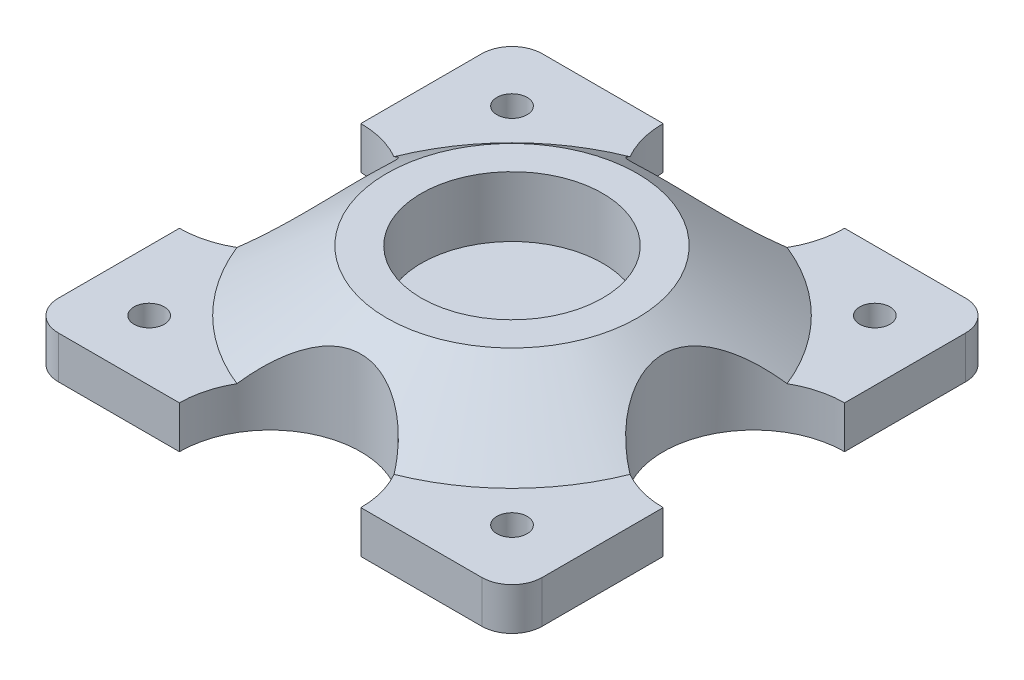
SolidWorks part; units mm, degrees
ref_plane "Front Plane" through (0, 0, 0) normal (0, 0, 1) x (1, 0, 0)
ref_plane "Top Plane" through (0, 0, 0) normal (0, 1, 0) x (1, 0, 0)
ref_plane "Right Plane" through (0, 0, 0) normal (1, 0, 0) x (0, 0, -1)
sketch "Sketch1" plane through (0, 0, 0) normal (0, 1, 0) x (1, 0, 0)
  line L1 (50.8, -50.8) -> (-50.8, -50.8)
  line L2 (50.8, -50.8) -> (50.8, 50.8)
  line L3 (50.8, 50.8) -> (-50.8, 50.8)
  line L4 (-50.8, -50.8) -> (-50.8, 50.8)
  line L5 (50.8, -50.8) -> (-50.8, 50.8) construction
  line L6 (50.8, 50.8) -> (-50.8, -50.8) construction
  point P0 (0, 0)
  dimension "D1" = 101.6
  dimension "D2" = 101.6
extrude "Boss-Extrude1" add sketch "Sketch1" along normal blind 8.89
sketch "Sketch2" plane through (0, 8.89, 0) normal (0, 1, 0) x (1, 0, 0)
  circle A0 centre (0, 0) radius 44.45
  dimension "D1" = 88.9
extrude "Boss-Extrude2" add sketch "Sketch2" along normal blind 12.7
sketch "Sketch5" plane through (0, 8.89, 0) normal (0, 1, 0) x (1, 0, 0)
  line L0 (-50.8, 50.8) -> (-50.8, -50.8) construction
  line L1 (50.8, 50.8) -> (-50.8, 50.8) construction
  line L2 (50.8, -50.8) -> (50.8, 50.8) construction
  line L3 (-50.8, -50.8) -> (50.8, -50.8) construction
  circle A0 centre (-38.1, 38.1) radius 3.175
  circle A1 centre (38.1, 38.1) radius 3.175
  circle A2 centre (-38.1, -38.1) radius 3.175
  circle A3 centre (38.1, -38.1) radius 3.175
  dimension "D1" = 6.35
  dimension "D2" = 12.7
  dimension "D3" = 12.7
  dimension "D4" = 12.7
  dimension "D5" = 12.7
  dimension "D6" = 12.7
  dimension "D7" = 12.7
  dimension "D8" = 12.7
  dimension "D9" = 12.7
fillet "Fillet1" radius 6.35 4 edges at (50.8, 4.445, -50.8) (-50.8, 4.445, -50.8) (50.8, 4.445, 50.8) (-50.8, 4.445, 50.8)
extrude "Cut-Extrude1" cut sketch "Sketch5" against normal through all
chamfer "Chamfer1" distance 12.7 angle 55 1 edges at (0, 21.59, 44.45) first distance on face at (0, 21.59, 44.45)
sketch "Sketch6" plane through (0, 21.59, 0) normal (0, 1, 0) x (1, 0, 0)
  circle A0 centre (0, 0) radius 19.05
  circle A2 centre (0, 0) radius 26.3125 construction
  dimension "D1" = 38.1
extrude "Cut-Extrude2" cut sketch "Sketch6" against normal blind 12.7
sketch "Sketch7" plane through (0, 0, 0) normal (0, 1, 0) x (1, 0, 0)
  line L0 (-50.8, 44.45) -> (-50.8, -44.45) construction
  line L1 (44.45, 50.8) -> (-44.45, 50.8) construction
  line L2 (50.8, -44.45) -> (50.8, 44.45) construction
  line L3 (-44.45, -50.8) -> (44.45, -50.8) construction
  circle A0 centre (-50.8, 0) radius 19.05
  circle A1 centre (0, 50.8) radius 19.05
  circle A2 centre (50.8, 0) radius 19.05
  circle A3 centre (0, -50.8) radius 19.05
extrude "Cut-Extrude3" cut sketch "Sketch7" along normal through all
